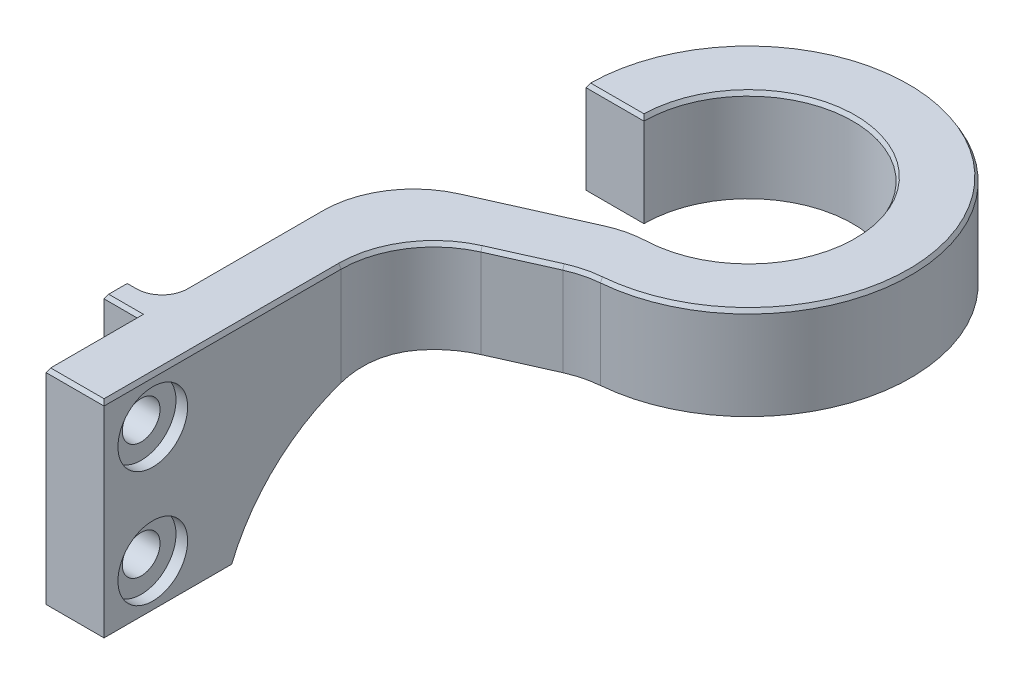
SolidWorks part; units mm, degrees
ref_plane "Front Plane" through (0, 0, 0) normal (0, 0, 1) x (1, 0, 0)
ref_plane "Top Plane" through (0, 0, 0) normal (0, 1, 0) x (1, 0, 0)
ref_plane "Right Plane" through (0, 0, 0) normal (1, 0, 0) x (0, 0, -1)
sketch "Sketch1" plane through (0, 0, 0) normal (0, 1, 0) x (1, 0, 0)
  line L1 (-16, -15.6588) -> (-16, -44.5201)
  line L2 (-16, -44.5201) -> (-11, -44.5201)
  line L3 (-9, 0) -> (-14, 0)
  line L4 (-11, -44.5201) -> (-11, -18.9041)
  line L5 (-11, -18.9041) -> (0, -14)
  line L6 (-16, -15.6588) -> (-0.9511, -8.9496)
  arc A0 (-0.9511, -8.9496) -> (-9, 0) centre (0, 0) ccw
  arc A1 (0, -14) -> (-14, 0) centre (0, 0) ccw
  dimension "D1" = 18
  dimension "D2" = 5
  dimension "D3" = 5
  dimension "D4" = 5
extrude "Boss-Extrude1" add sketch "Sketch1" along normal blind 8
sketch "Sketch2" plane through (-16, 0, 0) normal (-1, 0, 0) x (0, 0, 1)
  line L0 (44.5201, 0) -> (44.5201, -9.6498)
  line L1 (44.5201, 0) -> (18.9041, 0) construction
  line L2 (44.5201, -9.6498) -> (33.5201, -9.6498)
  line L3 (44.5201, 0) -> (19.1132, 0)
  line L4 (44.5201, 8) -> (44.5201, 0) construction
  line L5 (15.6588, 0) -> (44.5201, 0) construction
  arc A0 (33.5201, -9.6498) -> (19.1132, 0) centre (19.1132, -15.5794) ccw
  dimension "D1" = 11
extrude "Boss-Extrude2" add sketch "Sketch2" against normal blind 5
fillet "Fillet1" radius 8 4 edges at (-0.9511, 4, 8.9496) (0, 4, 14) (-16, 4, 15.6588) (-11, 4, 18.9041)
sketch "Sketch3" plane through (-11, 0, 0) normal (1, 0, 0) x (0, 0, -1)
  circle A0 centre (-40.3201, 4) radius 1.625
  circle A1 centre (-40.3201, -6) radius 1.625
  dimension "D1" = 3.25
extrude "Cut-Extrude1" cut sketch "Sketch3" against normal through all
sketch "Sketch4" plane through (-11, 0, 0) normal (1, 0, 0) x (0, 0, -1)
  circle A0 centre (-40.3201, 4) radius 3
  circle A1 centre (-40.3201, -6) radius 3
  dimension "D2" = 6
extrude "Cut-Extrude2" cut sketch "Sketch4" against normal blind 1
sketch "Sketch5" plane through (-16, 0, 0) normal (-1, 0, 0) x (0, 0, 1)
  line L0 (20.8512, 8) -> (44.5201, 8) construction
  line L1 (36.5201, 8) -> (34.5201, 8)
  line L2 (36.5201, 8) -> (36.5201, -9.6498)
  line L3 (36.5201, -9.6498) -> (34.5201, -9.6498)
  line L4 (34.5201, 8) -> (34.5201, -9.6498)
  line L6 (33.5201, -9.6498) -> (44.5201, -9.6498) construction
  dimension "D1" = 2
extrude "Boss-Extrude3" add sketch "Sketch5" along normal blind 3
fillet "Fillet2" radius 2 1 edges at (-16, -0.8249, 34.5201)
chamfer "Chamfer1" distance 0.2 angle 60 17 edges at (-19, 8, 35.5201) (-17.5, 8, 36.5201) (-16, 8, 40.5201) (-13.5, 8, 44.5201) (-11.5, 8, 0) (9.4662, 8, -10.3146) (-0.1153, 8, 14.173) (-11, 8, 34.3083) (-3.8156, 8, 15.7011) (-9.7104, 8, 19.741) (6.2377, 8, -6.4878) (-1.1508, 8, 9.1963) (-18.5, 8, 34.5201) (-6.9236, 8, 11.6123) (-16.5858, 8, 33.9343) (-16, 8, 26.6857) (-14.7104, 8, 16.4958) first distance on face at (-9.4299, 8, 20.9792)
